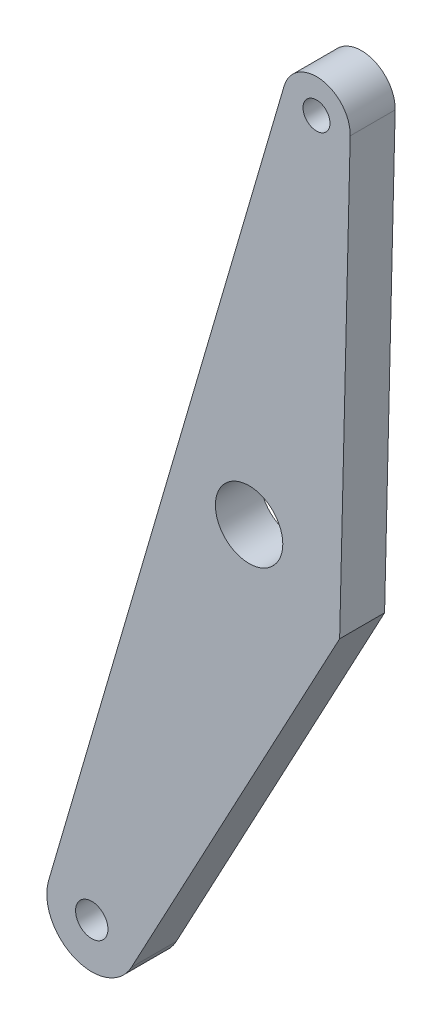
SolidWorks part; units mm, degrees
ref_plane "Front Plane" through (0, 0, 0) normal (0, 0, 1) x (1, 0, 0)
ref_plane "Top Plane" through (0, 0, 0) normal (0, 1, 0) x (1, 0, 0)
ref_plane "Right Plane" through (0, 0, 0) normal (1, 0, 0) x (0, 0, -1)
sketch "Sketch1" plane through (0, 0, 0) normal (0, 0, 1) x (1, 0, 0)
  line L0 (-6.095, 1.7813) -> (27.1787, 115.6359)
  line L6 (0, 0) -> (50.8, 0) construction
  line L7 (35.0174, 51.9098) -> (36.5111, 114.1858)
  line L8 (22.225, 59.4836) -> (0, 0) construction
  line L11 (5.5972, -2.999) -> (35.0174, 51.9098)
  circle A0 centre (0, 0) radius 2.286
  arc A1 (-6.095, 1.7813) -> (5.5972, -2.999) centre (0, 0) ccw
  circle A3 centre (31.75, 114.3) radius 1.905
  arc A5 (36.5111, 114.1858) -> (27.1787, 115.6359) centre (31.75, 114.3) ccw
  circle A6 centre (22.225, 59.4836) radius 4.7625
  dimension "D1" = 12.7
  dimension "D2" = 4.572
  dimension "D8" = 63.5
  dimension "D9" = 22.225
  dimension "D5" = 25.4
  dimension "D6" = 3.81
  dimension "D3" = 9.525
  dimension "D10" = 9.525
  dimension "D4" = 31.75
  dimension "D7" = 114.3
extrude "Boss-Extrude1" add sketch "Sketch1" along normal blind 6.35
